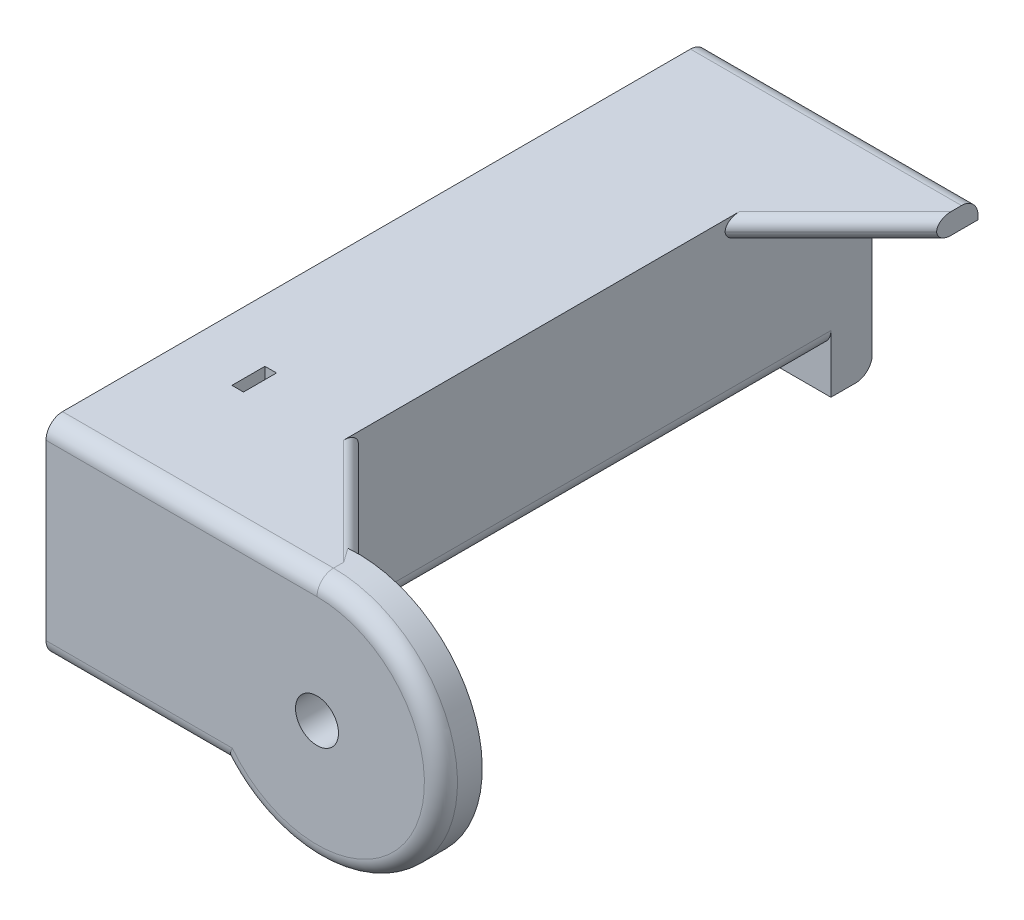
SolidWorks part; units mm, degrees
ref_plane "Front Plane" through (0, 0, 0) normal (0, 0, 1) x (1, 0, 0)
ref_plane "Top Plane" through (0, 0, 0) normal (0, 1, 0) x (1, 0, 0)
ref_plane "Right Plane" through (0, 0, 0) normal (1, 0, 0) x (0, 0, -1)
sketch "Sketch1" plane through (0, 0, 0) normal (0, 1, 0) x (1, 0, 0)
  line L0 (12.7, 50.8) -> (-12.7, -50.8) construction
  line L1 (-12.7, 50.8) -> (12.7, 50.8)
  line L2 (-12.7, 50.8) -> (-12.7, -50.8)
  line L3 (-12.7, -50.8) -> (12.7, -50.8)
  line L4 (12.7, 50.8) -> (12.7, -50.8)
  dimension "D1" = 25.4
  dimension "D2" = 101.6
extrude "Top" add sketch "Sketch1" along normal blind 4.7625
sketch "Sketch2" plane through (0, 4.7625, 0) normal (0, 1, 0) x (1, 0, 0)
  line L1 (-12.7, 50.8) -> (12.7, 50.8)
  line L2 (-12.7, 50.8) -> (-12.7, -50.8)
  line L3 (-12.7, -50.8) -> (12.7, -50.8)
  line L5 (12.7, 50.8) -> (12.7, -50.8)
  line L6 (-7.9375, 44.45) -> (7.9375, 44.45)
  line L7 (-7.9375, 44.45) -> (-7.9375, -44.45)
  line L8 (-7.9375, -44.45) -> (7.9375, -44.45)
  line L9 (7.9375, 44.45) -> (7.9375, -44.45)
  dimension "D1" = 4.7625
  dimension "D2" = 4.7625
  dimension "D3" = 6.35
  dimension "D4" = 6.35
extrude "Walls" add sketch "Sketch2" against normal blind 31.75
sketch "Sketch9" plane through (0, 0, 50.8) normal (0, 0, -1) x (-1, 0, 0)
  line L0 (-28.956, -14.2875) -> (-12.7, -14.2875) construction
  line L2 (12.7, -26.9875) -> (-12.7, -26.9875) construction
  line L3 (-28.956, 4.7625) -> (-12.7, 4.7625)
  line L8 (-12.7, -26.9875) -> (-12.7, 4.7625)
  line L14 (-14.757, -26.9875) -> (-12.7, -26.9875)
  circle A0 centre (-28.956, -14.2875) radius 19.05 construction
  arc A1 (-28.956, 4.7625) -> (-14.757, -26.9875) centre (-28.956, -14.2875) ccw
  circle A2 centre (-28.956, -14.2875) radius 3.302
  dimension "D2" = 19.05
  dimension "D3" = 6.604
  dimension "D1" = 16.256
extrude "Joint Hinge" add sketch "Sketch9" along normal blind 6.35
sketch "Sketch3" plane through (-12.7, 0, 0) normal (-1, 0, 0) x (0, 0, 1)
  line L0 (-50.8, -11.1125) -> (-31.75, -11.1125) construction
  line L1 (-50.8, 4.7625) -> (-50.8, -26.9875) construction
  line L2 (50.8, -11.1125) -> (38.1, -11.1125) construction
  line L3 (50.8, 4.7625) -> (50.8, -26.9875) construction
  line L4 (-31.75, -11.1125) -> (-31.75, -26.9875) construction
  line L9 (-50.8, -26.9875) -> (50.8, -26.9875) construction
  line L11 (-25.6016, -12.7) -> (-23.0616, -12.7)
  line L13 (-25.6016, -9.525) -> (-23.0616, -9.525)
  line L14 (-23.0616, -12.7) -> (-23.0616, -9.525)
  line L15 (-25.6016, -12.7) -> (-23.0616, -9.525) construction
  line L16 (-25.6016, -9.525) -> (-23.0616, -12.7) construction
  circle A0 centre (38.1, -11.1125) radius 3.175
  circle A1 centre (-31.75, -11.1125) radius 6.35 construction
  arc A2 (-25.6016, -9.525) -> (-25.6016, -12.7) centre (-31.75, -11.1125) ccw
  point P13 (-24.3316, -11.1125)
  dimension "D3" = 6.35
  dimension "D4" = 12.7
  dimension "D1" = 19.05
  dimension "D2" = 12.7
  dimension "D5" = 15.875
  dimension "D6" = 3.175
  dimension "D7" = 2.54
extrude "Shaft holes" cut sketch "Sketch3" against normal blind 23.876
sketch "Sketch13" plane through (0, 0, 0) normal (0, -1, 0) x (1, 0, 0)
  line L1 (-3.175, 26.67) -> (-1.397, 26.67)
  line L2 (-3.175, 26.67) -> (-3.175, 31.75)
  line L3 (-3.175, 31.75) -> (-1.397, 31.75)
  line L4 (-1.397, 26.67) -> (-1.397, 31.75)
  line L5 (-12.7, 50.8) -> (12.7, 50.8) construction
  line L6 (-12.7, -50.8) -> (-12.7, 50.8) construction
  dimension "D1" = 1.778
  dimension "D2" = 5.08
  dimension "D3" = 19.05
  dimension "D4" = 9.525
extrude "Wire Loft Mount" cut sketch "Sketch13" against normal blind 12.7
sketch "Sketch15" plane through (0, 4.7625, 0) normal (0, 1, 0) x (1, 0, 0)
  line L0 (12.7, -44.45) -> (28.956, -44.45)
  line L1 (28.956, -44.45) -> (12.7, -28.194)
  line L2 (12.7, -44.45) -> (12.7, 50.8) construction
  line L3 (12.7, -28.194) -> (12.7, -44.45)
  line L4 (12.7, 28.194) -> (28.956, 44.45)
  line L5 (28.956, 44.45) -> (28.956, 50.8)
  line L6 (28.956, 50.8) -> (12.7, 50.8)
  line L7 (12.7, 50.8) -> (12.7, 28.194)
  dimension "D1" = 45
  dimension "D2" = 6.35
  dimension "D3" = 45
extrude "Anti-flex" add sketch "Sketch15" against normal blind 3.175
sketch "Sketch16" plane through (12.7, 0, 0) normal (1, 0, 0) x (0, 0, -1)
  line L0 (44.45, -26.9875) -> (44.45, 0) construction
  line L1 (44.45, -44.429) -> (-44.45, -44.429)
  line L2 (44.45, -44.429) -> (44.45, -20.6375)
  line L3 (44.45, -20.6375) -> (-44.45, -20.6375)
  line L4 (-44.45, -44.429) -> (-44.45, -20.6375)
  line L5 (-44.45, -26.9875) -> (-44.45, 0) construction
  line L6 (-44.45, -26.9875) -> (50.8, -26.9875) construction
  dimension "D1" = 6.35
extrude "Far-Trim" cut sketch "Sketch16" against normal up to next
fillet "Fillet1" radius 2.54 6 edges at (0, -26.9875, -50.8) (1.0285, -26.9875, 50.8) (46.3462, -22.0646, 50.8) (8.128, 4.7625, 50.8) (8.128, 4.7625, -50.8) (12.7, -20.6375, 0)
fillet "Fillet2" radius 1.5875 4 edges at (20.828, 1.5875, -36.322) (20.828, 4.7625, -36.322) (20.828, 1.5875, 36.322) (20.828, 4.7625, 36.322)
